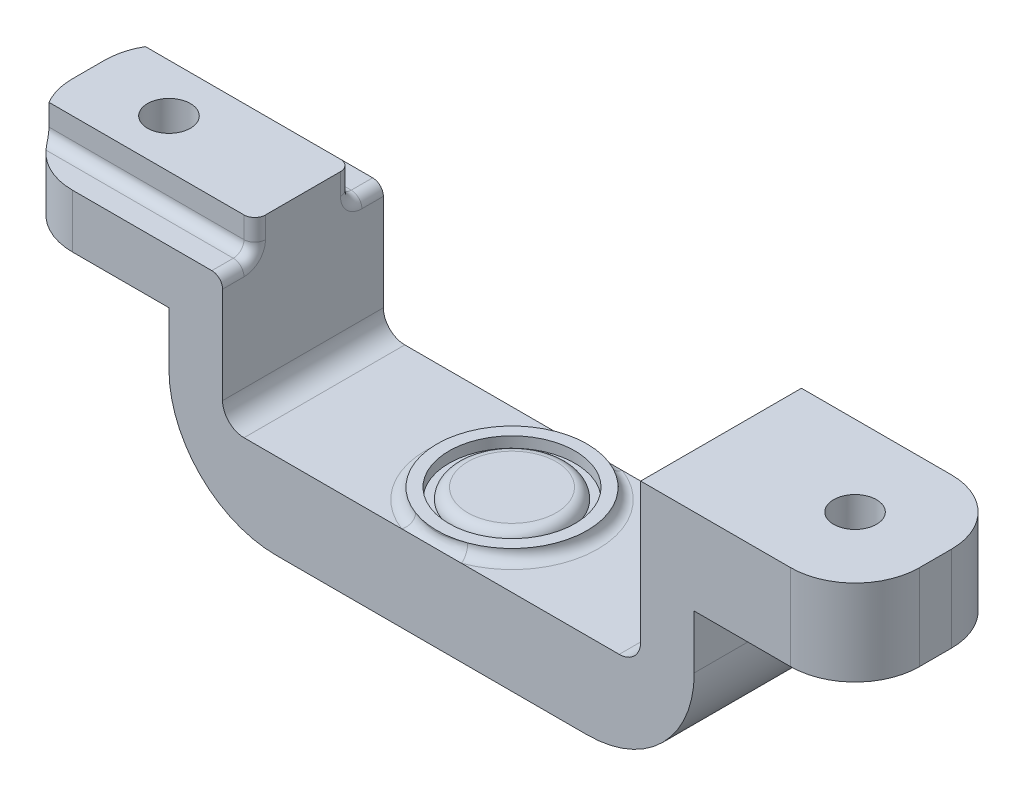
SolidWorks part; units mm, degrees
ref_plane "Спереди" through (0, 0, 0) normal (0, 0, 1) x (1, 0, 0)
ref_plane "Сверху" through (0, 0, 0) normal (0, 1, 0) x (1, 0, 0)
ref_plane "Справа" through (0, 0, 0) normal (1, 0, 0) x (0, 0, -1)
sketch "Sketch1" plane through (0, 0, 0) normal (0, 1, 0) x (1, 0, 0)
  line L1 (0, 0) -> (39, 0)
  line L2 (0, 0) -> (0, -15)
  line L3 (0, -15) -> (39, -15)
  line L4 (39, 0) -> (39, -15)
  dimension "D1" = 15
  dimension "D2" = 39
extrude "Boss-Extrude1" add sketch "Sketch1" along normal blind 8 contours L2 L3 L4 L1
sketch "Sketch2" plane through (0, 8, 0) normal (0, 1, 0) x (1, 0, 0)
  line L0 (19.5, 0) -> (19.5, -15) construction
  line L1 (0, 0) -> (39, 0) construction
  line L2 (0, -15) -> (39, -15) construction
  circle A0 centre (19.5, -7.5) radius 5.875
  circle A1 centre (19.5, -7.5) radius 5.125
  circle A2 centre (19.5, -7.5) radius 7
  dimension "D1" = 11.75
  dimension "D2" = 10.25
  dimension "D3" = 14
extrude "Boss-Extrude2" add sketch "Sketch2" along normal blind 1 contours L0 A2 A0 | A2 L0 A0 | L0 A1 | A1 L0 region at (24.3391, 8, 2.6609) region at (19.3435, 8, 1.0625) region at (21.6751, 8, 7.5) region at (17.3249, 8, 7.5)
fillet "Fillet1" radius 1 1 edges at (19.5, 9, 12.625)
fillet "Fillet2" radius 1 1 edges at (19.5, 8, 0.5)
sketch "Sketch3" plane through (0, 0, 0) normal (0, -1, 0) x (1, 0, 0)
  line L1 (0, 15) -> (-5, 15)
  line L2 (0, 15) -> (0, 0)
  line L3 (0, 0) -> (-5, 0)
  line L4 (-5, 15) -> (-5, 0)
  line L5 (39, 15) -> (44, 15)
  line L6 (39, 15) -> (39, 0)
  line L7 (39, 0) -> (44, 0)
  line L8 (44, 15) -> (44, 0)
  dimension "D1" = 5
  dimension "D2" = 5
  dimension "D3" = 15
  dimension "D4" = 15
extrude "Boss-Extrude3" add sketch "Sketch3" against normal blind 23
fillet "Fillet3" radius 2 2 edges
fillet "Fillet4" radius 10 2 edges at (44, 0, 7.5) (-5, 0, 7.5)
sketch "Sketch4" plane through (0, 23, 0) normal (0, 1, 0) x (1, 0, 0)
  line L0 (19.5, 0) -> (19.5, -15) construction
  line L1 (16.7161, 0) -> (22.2839, 0) construction
  line L2 (16.7161, -15) -> (22.2839, -15) construction
  line L3 (-5, -7.5) -> (44, -7.5) construction
  line L4 (-5, -15) -> (-5, 0) construction
  line L5 (44, 0) -> (44, -15) construction
  line L6 (-20, 0) -> (-5, -15) construction
  line L7 (-5, 0) -> (-20, 0)
  line L8 (-5, 0) -> (-5, -15)
  line L9 (-5, -15) -> (-20, -15)
  line L10 (-20, 0) -> (-20, -15)
  line L11 (44, 0) -> (59, 0)
  line L12 (44, 0) -> (44, -15)
  line L13 (44, -15) -> (59, -15)
  line L14 (59, 0) -> (59, -15)
  line L15 (44, -15) -> (59, 0) construction
  circle A0 centre (51.5, -7.5) radius 2
  circle A1 centre (-12.5, -7.5) radius 2
  dimension "D5" = 4
  dimension "D6" = 4
  dimension "D1" = 15
  dimension "D2" = 15
  dimension "D3" = 15
  dimension "D4" = 15
extrude "Boss-Extrude4" add sketch "Sketch4" against normal blind 8
sketch "Sketch5" plane through (0, 15, 0) normal (0, -1, 0) x (1, 0, 0)
  circle A0 centre (-12.5, 7.5) radius 3.5
  circle A1 centre (51.5, 7.5) radius 3.5
  dimension "D1" = 7
  dimension "D2" = 7
extrude "Cut-Extrude1" cut sketch "Sketch5" against normal blind 4
sketch "Sketch6" plane through (0, 23, 0) normal (0, 1, 0) x (1, 0, 0)
  line L0 (-20, -7.5) -> (19.5, -7.5) construction
  line L1 (-20, 0) -> (-20, -15) construction
  line L2 (19.5, -7.5) -> (19.5, 0) construction
  line L3 (16.7161, 0) -> (22.2839, 0) construction
  line L4 (19.5, -7.5) -> (19.5, -15) construction
  line L5 (16.7161, -15) -> (22.2839, -15) construction
  line L6 (19.5, -3) -> (19.5, 0)
  line L7 (19.5, -12) -> (-20, -12)
  line L8 (19.5, -12) -> (19.5, -15)
  line L9 (19.5, -15) -> (-20, -15)
  line L10 (-20, -12) -> (-20, -15)
  line L11 (19.5, -3) -> (-20, -3)
  line L12 (19.5, 0) -> (-20, 0)
  line L13 (-20, -3) -> (-20, 0)
  dimension "D1" = 3
extrude "Cut-Extrude2" cut sketch "Sketch6" against normal blind 3
fillet "Fillet5" radius 1 6 edges at (0, 21.5, 3) (-10, 20, 12) (0, 20, 13.5) (0, 21.5, 12) (0, 20, 1.5) (-10, 20, 3)
fillet "Fillet6" radius 6 4 edges at (59, 19, 15) (59, 19, 0) (-20, 17.5, 15) (-20, 17.5, 0)
